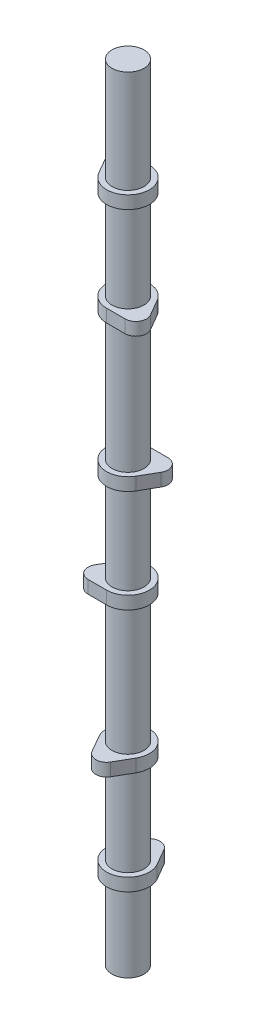
SolidWorks part; units mm, degrees
ref_plane "Front Plane" through (0, 0, 0) normal (0, 0, 1) x (1, 0, 0)
ref_plane "Top Plane" through (0, 0, 0) normal (0, 1, 0) x (1, 0, 0)
ref_plane "Right Plane" through (0, 0, 0) normal (1, 0, 0) x (0, 0, -1)
sketch "Sketch1" plane through (0, 0, 0) normal (0, 1, 0) x (1, 0, 0)
  line L0 (-5.4993, 15.875) -> (-10.9985, 6.35)
  line L1 (5.4993, 15.875) -> (10.9985, 6.35)
  arc A0 (-10.9985, 6.35) -> (10.9985, 6.35) centre (0, 0) ccw
  arc A1 (5.4993, 15.875) -> (-5.4993, 15.875) centre (0, 12.7) ccw
  dimension "D1" = 12.7
  dimension "D3" = 25.4
  dimension "D2" = 12.7
extrude "Boss-Extrude1" add sketch "Sketch1" along normal blind 7.62
ref_axis "Axis1" through (0, 36.8908, 0) along (0, -1, 0)
pattern_linear "LPattern1" count 2 spacing 60.96 along (0, 1, 0) of bodies 101
move or copy body "Body-Move/Copy1" bodies to move or copy 102 copy no rotation origin (0, 0, 0) rotation axis (0, 1, 0) rotation angle 180
pattern_linear "LPattern2" count 3 spacing 145.05 along (0, 1, 0) of bodies 101 103
move or copy body "Body-Move/Copy2" bodies to move or copy 106 104 copy no rotation origin (0, 0, 0) rotation axis (0, 1, 0) rotation angle 120
move or copy body "Body-Move/Copy3" bodies to move or copy 107 105 copy no rotation origin (0, 0, 0) rotation axis (0, -1, 0) rotation angle 120
sketch "Sketch2" plane through (0, 0, 0) normal (0, 1, 0) x (1, 0, 0)
  circle A0 centre (0, 0) radius 9.5
  dimension "D1" = 19
extrude "Boss-Extrude2" add sketch "Sketch2" along normal blind 466.09 from offset 46.53 offset against normal yes
